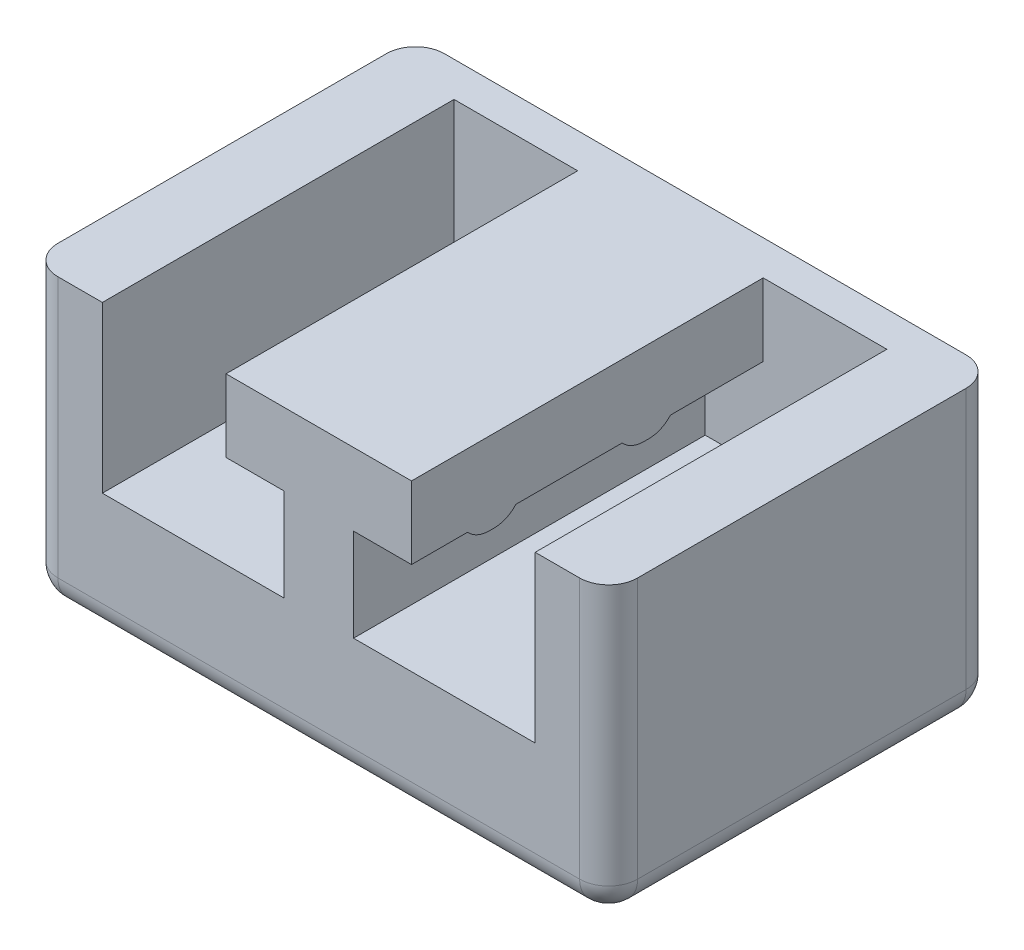
SolidWorks part; units mm, degrees
ref_plane "Front Plane" through (0, 0, 0) normal (0, 0, 1) x (1, 0, 0)
ref_plane "Top Plane" through (0, 0, 0) normal (0, 1, 0) x (1, 0, 0)
ref_plane "Right Plane" through (0, 0, 0) normal (1, 0, 0) x (0, 0, -1)
sketch "Sketch2" plane through (0, 0, 0) normal (0, 1, 0) x (1, 0, 0)
  line L1 (-15, 10) -> (15, 10)
  line L2 (-15, 10) -> (-15, -10)
  line L3 (-15, -10) -> (15, -10)
  line L4 (15, 10) -> (15, -10)
  line L5 (-15, 10) -> (15, -10) construction
  line L6 (-15, -10) -> (15, 10) construction
  point P0 (0, 0)
  dimension "D1" = 30
  dimension "D2" = 20
extrude "Boss-Extrude1" add sketch "Sketch2" along normal blind 15
sketch "Sketch3" plane through (0, 0, 10) normal (0, 0, 1) x (1, 0, 0)
  line L0 (-11.2, 15) -> (-11.2, 6.45)
  line L1 (-15, 15) -> (15, 15) construction
  line L2 (-11.2, 6.45) -> (-1.8, 6.45)
  line L3 (-1.8, 6.45) -> (-1.8, 11.25)
  line L4 (-1.8, 11.25) -> (-4.8, 11.25)
  line L5 (-4.8, 11.25) -> (-4.8, 15)
  line L6 (-4.8, 15) -> (-11.2, 15)
  line L8 (-15, 15) -> (-15, 0) construction
  point P10 (-8, 15)
  dimension "D1" = 3.75
  dimension "D2" = 9.4
  dimension "D3" = 4.8
  dimension "D4" = 7
  dimension "D5" = 6.4
  dimension "D6" = 1.8
extrude "Cut-Extrude1" cut sketch "Sketch3" against normal blind 18.2
sketch "Sketch4" plane through (-1.8, 0, 0) normal (-1, 0, 0) x (0, 0, 1)
  line L0 (-8.2, 11.25) -> (10, 11.25) construction
  line L1 (4.6, 11.25) -> (7.1, 11.25)
  line L2 (4.6, 11.25) -> (4.6, 10.75)
  line L3 (4.6, 10.75) -> (7.1, 10.75)
  line L4 (7.1, 11.25) -> (7.1, 10.75)
  line L6 (10, 6.45) -> (10, 11.25) construction
  line L7 (-3.4, 11.25) -> (-0.9, 11.25)
  line L8 (-0.9, 11.25) -> (-0.9, 10.75)
  line L9 (-3.4, 11.25) -> (-3.4, 10.75)
  line L10 (-3.4, 10.75) -> (-0.9, 10.75)
  line L12 (-8.2, 11.25) -> (-8.2, 15) construction
  point P6 (5.85, 11.25)
  point P14 (-2.15, 11.25)
  dimension "D1" = 2.5
  dimension "D2" = 0.5
  dimension "D3" = 4.15
  dimension "D4" = 2.5
  dimension "D5" = 0.5
  dimension "D6" = 6.05
extrude "Boss-Extrude2" add sketch "Sketch4" along normal blind 3
fillet "Fillet1" radius 1.5 4 edges at (-3.3, 10.75, 4.6) (-3.3, 10.75, 7.1) (-3.3, 10.75, -3.4) (-3.3, 10.75, -0.9)
ref_plane "Plane2" through (0, 0, 0.9) normal (0, 0, 1) x (1, 0, 0)
mirror "Mirror2" about plane through (0, 0, 0) normal (1, 0, 0) of "Cut-Extrude1", "Boss-Extrude2", "Fillet1"
fillet "Fillet2" radius 1.5 8 edges at (0, 0, -10) (-15, 0, 0) (0, 0, 10) (15, 0, 0) (-15, 7.5, -10) (-15, 7.5, 10) (15, 7.5, 10) (15, 7.5, -10)
